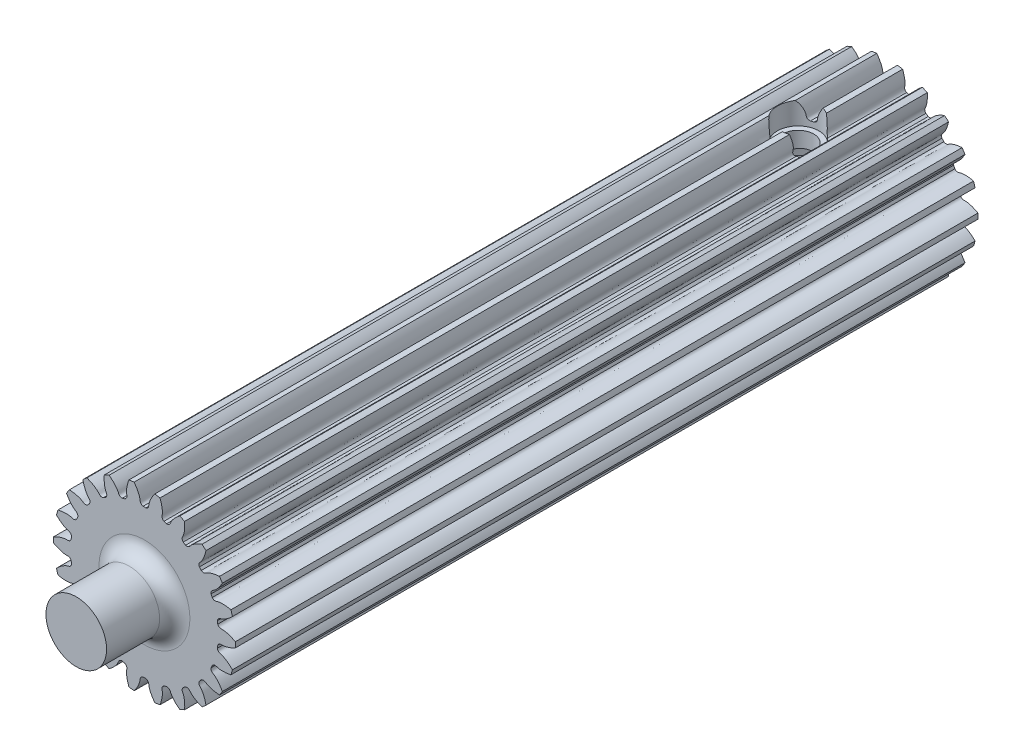
SolidWorks part; units mm, degrees
ref_plane "前视基准面" through (0, 0, 0) normal (0, 0, 1) x (1, 0, 0)
ref_plane "上视基准面" through (0, 0, 0) normal (0, 1, 0) x (1, 0, 0)
ref_plane "右视基准面" through (0, 0, 0) normal (1, 0, 0) x (0, 0, -1)
sketch "草图1" plane through (0, 0, 0) normal (0, 0, 1) x (1, 0, 0)
  circle A0 centre (0, 0) radius 12
extrude "凸台-拉伸1" add sketch "草图1" along normal blind 30
ref_axis "基准轴1" through (0, 0, -1.5) along (0, 0, 1)
sketch "草图2" plane through (0, 0, 0) normal (0, 0, 1) x (1, 0, 0)
  line L0 (0, 0) -> (0, 12) construction
  circle A0 centre (0, 0) radius 12 construction
  arc A1 (0.1857, 9.7482) -> (-0.1857, 9.7482) centre (0, 0) ccw
  arc A2 (3.0856, 13.5599) -> (-3.0856, 13.5599) centre (0, 0) ccw
  spline S0 degree 3 poles (0.1857, 9.7482) (0.5882, 9.8762) (0.5483, 10.1518) (0.5996, 10.4216) (0.606, 10.4519) (0.6139, 10.4862) (0.6235, 10.5243) (0.6349, 10.5661) (0.6484, 10.6117) (0.664, 10.661) (0.6819, 10.7139) (0.7023, 10.7703) (0.7253, 10.8301) (0.7511, 10.8933) (0.7797, 10.9597) (0.8114, 11.0293) (0.8462, 11.1021) (0.8843, 11.1778) (0.9259, 11.2563) (0.9711, 11.3377) (1.0199, 11.4217) (1.0726, 11.5082) (1.1292, 11.5972) (1.1899, 11.6884) (1.2547, 11.7818) (1.3238, 11.8773) (1.3973, 11.9746) (1.4753, 12.0737) (1.5579, 12.1744) (1.6452, 12.2766) (1.7372, 12.3802) (1.8341, 12.4849) (1.9359, 12.5906) (2.0428, 12.6972) (2.1547, 12.8044) (2.2718, 12.9123) (2.3942, 13.0205) (2.5218, 13.1289) (2.6548, 13.2373) (2.8415, 13.3834) (2.9864, 13.49) (3.0856, 13.5599) knots 0 0 0 0 0.157021 0.162531 0.168888 0.176093 0.184146 0.193046 0.202794 0.213389 0.224833 0.237123 0.250262 0.264248 0.279082 0.294763 0.311292 0.328669 0.346893 0.365965 0.385884 0.406652 0.428266 0.450729 0.474039 0.498197 0.523202 0.549055 0.575756 0.603304 0.6317 0.660944 0.691035 0.721974 0.75376 0.786395 0.819876 0.854206 0.889383 0.925408 1 1 1 1
  spline S1 degree 3 poles (-0.1857, 9.7482) (-0.5882, 9.8762) (-0.5483, 10.1518) (-0.5996, 10.4216) (-0.606, 10.4519) (-0.6139, 10.4862) (-0.6235, 10.5243) (-0.6349, 10.5661) (-0.6484, 10.6117) (-0.664, 10.661) (-0.6819, 10.7139) (-0.7023, 10.7703) (-0.7253, 10.8301) (-0.7511, 10.8933) (-0.7797, 10.9597) (-0.8114, 11.0293) (-0.8462, 11.1021) (-0.8843, 11.1778) (-0.9259, 11.2563) (-0.9711, 11.3377) (-1.0199, 11.4217) (-1.0726, 11.5082) (-1.1292, 11.5972) (-1.1899, 11.6884) (-1.2547, 11.7818) (-1.3238, 11.8773) (-1.3973, 11.9746) (-1.4753, 12.0737) (-1.5579, 12.1744) (-1.6452, 12.2766) (-1.7372, 12.3802) (-1.8341, 12.4849) (-1.9359, 12.5906) (-2.0428, 12.6972) (-2.1547, 12.8044) (-2.2718, 12.9123) (-2.3942, 13.0205) (-2.5218, 13.1289) (-2.6548, 13.2373) (-2.8415, 13.3834) (-2.9864, 13.49) (-3.0856, 13.5599) knots 0 0 0 0 0.157021 0.162531 0.168888 0.176093 0.184146 0.193046 0.202794 0.213389 0.224833 0.237123 0.250262 0.264248 0.279082 0.294763 0.311292 0.328669 0.346893 0.365965 0.385884 0.406652 0.428266 0.450729 0.474039 0.498197 0.523202 0.549055 0.575756 0.603304 0.6317 0.660944 0.691035 0.721974 0.75376 0.786395 0.819876 0.854206 0.889383 0.925408 1 1 1 1
extrude "切除-拉伸1" cut sketch "草图2" along normal through all
pattern_circular "阵列(圆周)1" count 22 every 16.364 about axis through (0, 0, -1.5) along (0, 0, 1) of "切除-拉伸1"
sketch "草图3" plane through (0, 0, 0) normal (0, 0, 1) x (1, 0, 0)
  circle A0 centre (0, 0) radius 11 construction
  dimension "Dn" = 22
sketch "草图4" plane through (0, 0, 0) normal (0, 0, -1) x (-1, 0, 0)
  arc A45 (2.9245, 9.3011) -> (2.5682, 9.4057) centre (0, 0) ccw
  arc A46 (2.0557, 11.8226) -> (1.3584, 11.9229) centre (0, 0) ccw
  arc A47 (0.1857, 9.7482) -> (-0.1857, 9.7482) centre (0, 0) ccw
  arc A48 (-1.3584, 11.9229) -> (-2.0557, 11.8226) centre (0, 0) ccw
  arc A49 (-2.5682, 9.4057) -> (-2.9245, 9.3011) centre (0, 0) ccw
  arc A50 (-4.6624, 11.0572) -> (-5.3032, 10.7646) centre (0, 0) ccw
  arc A51 (-5.1141, 8.3011) -> (-5.4265, 8.1004) centre (0, 0) ccw
  arc A52 (-7.5887, 9.2958) -> (-8.1211, 8.8344) centre (0, 0) ccw
  arc A53 (-7.2456, 6.5241) -> (-7.4888, 6.2434) centre (0, 0) ccw
  arc A54 (-9.9003, 6.7812) -> (-10.2811, 6.1886) centre (0, 0) ccw
  arc A55 (-8.7902, 4.2184) -> (-8.9444, 3.8807) centre (0, 0) ccw
  arc A56 (-11.4097, 3.7173) -> (-11.6082, 3.0414) centre (0, 0) ccw
  arc A57 (-9.6226, 1.5711) -> (-9.6754, 1.2035) centre (0, 0) ccw
  arc A58 (-11.9948, 0.3522) -> (-11.9948, -0.3522) centre (0, 0) ccw
  arc A59 (-9.6754, -1.2035) -> (-9.6226, -1.5711) centre (0, 0) ccw
  arc A60 (-11.6082, -3.0414) -> (-11.4097, -3.7173) centre (0, 0) ccw
  arc A61 (-8.9444, -3.8807) -> (-8.7902, -4.2184) centre (0, 0) ccw
  arc A62 (-10.2811, -6.1886) -> (-9.9003, -6.7812) centre (0, 0) ccw
  arc A63 (-7.4888, -6.2434) -> (-7.2456, -6.5241) centre (0, 0) ccw
  arc A64 (-8.1211, -8.8344) -> (-7.5887, -9.2958) centre (0, 0) ccw
  arc A65 (-5.4265, -8.1004) -> (-5.1141, -8.3011) centre (0, 0) ccw
  arc A66 (-5.3032, -10.7646) -> (-4.6624, -11.0572) centre (0, 0) ccw
  arc A67 (-2.9245, -9.3011) -> (-2.5682, -9.4057) centre (0, 0) ccw
  arc A68 (-2.0557, -11.8226) -> (-1.3584, -11.9229) centre (0, 0) ccw
  arc A69 (-0.1857, -9.7482) -> (0.1857, -9.7482) centre (0, 0) ccw
  arc A70 (1.3584, -11.9229) -> (2.0557, -11.8226) centre (0, 0) ccw
  arc A71 (2.5682, -9.4057) -> (2.9245, -9.3011) centre (0, 0) ccw
  arc A72 (4.6624, -11.0572) -> (5.3032, -10.7646) centre (0, 0) ccw
  arc A73 (5.1141, -8.3011) -> (5.4265, -8.1004) centre (0, 0) ccw
  arc A74 (7.5887, -9.2958) -> (8.1211, -8.8344) centre (0, 0) ccw
  arc A75 (7.2456, -6.5241) -> (7.4888, -6.2434) centre (0, 0) ccw
  arc A76 (9.9003, -6.7812) -> (10.2811, -6.1886) centre (0, 0) ccw
  arc A77 (8.7902, -4.2184) -> (8.9444, -3.8807) centre (0, 0) ccw
  arc A78 (11.4097, -3.7173) -> (11.6082, -3.0414) centre (0, 0) ccw
  arc A79 (9.6226, -1.5711) -> (9.6754, -1.2035) centre (0, 0) ccw
  arc A80 (11.9948, -0.3522) -> (11.9948, 0.3522) centre (0, 0) ccw
  arc A81 (9.6754, 1.2035) -> (9.6226, 1.5711) centre (0, 0) ccw
  arc A82 (11.6082, 3.0414) -> (11.4097, 3.7173) centre (0, 0) ccw
  arc A83 (8.9444, 3.8807) -> (8.7902, 4.2184) centre (0, 0) ccw
  arc A84 (10.2811, 6.1886) -> (9.9003, 6.7812) centre (0, 0) ccw
  arc A85 (7.4888, 6.2434) -> (7.2456, 6.5241) centre (0, 0) ccw
  arc A86 (8.1211, 8.8344) -> (7.5887, 9.2958) centre (0, 0) ccw
  arc A87 (5.4265, 8.1004) -> (5.1141, 8.3011) centre (0, 0) ccw
  arc A88 (5.3032, 10.7646) -> (4.6624, 11.0572) centre (0, 0) ccw
  arc A89 (2.9245, 9.3011) -> (2.5682, 9.4057) centre (0, 0) ccw
  arc A90 (2.0557, 11.8226) -> (1.3584, 11.9229) centre (0, 0) ccw
  arc A91 (0.1857, 9.7482) -> (-0.1857, 9.7482) centre (0, 0) ccw
  arc A92 (-1.3584, 11.9229) -> (-2.0557, 11.8226) centre (0, 0) ccw
  arc A93 (-2.5682, 9.4057) -> (-2.9245, 9.3011) centre (0, 0) ccw
  arc A94 (-4.6624, 11.0572) -> (-5.3032, 10.7646) centre (0, 0) ccw
  arc A95 (-5.1141, 8.3011) -> (-5.4265, 8.1004) centre (0, 0) ccw
  arc A96 (-7.5887, 9.2958) -> (-8.1211, 8.8344) centre (0, 0) ccw
  arc A97 (-7.2456, 6.5241) -> (-7.4888, 6.2434) centre (0, 0) ccw
  arc A98 (-9.9003, 6.7812) -> (-10.2811, 6.1886) centre (0, 0) ccw
  arc A99 (-8.7902, 4.2184) -> (-8.9444, 3.8807) centre (0, 0) ccw
  arc A100 (-11.4097, 3.7173) -> (-11.6082, 3.0414) centre (0, 0) ccw
  arc A101 (-9.6226, 1.5711) -> (-9.6754, 1.2035) centre (0, 0) ccw
  arc A102 (-11.9948, 0.3522) -> (-11.9948, -0.3522) centre (0, 0) ccw
  arc A103 (-9.6754, -1.2035) -> (-9.6226, -1.5711) centre (0, 0) ccw
  arc A104 (-11.6082, -3.0414) -> (-11.4097, -3.7173) centre (0, 0) ccw
  arc A105 (-8.9444, -3.8807) -> (-8.7902, -4.2184) centre (0, 0) ccw
  arc A106 (-10.2811, -6.1886) -> (-9.9003, -6.7812) centre (0, 0) ccw
  arc A107 (-7.4888, -6.2434) -> (-7.2456, -6.5241) centre (0, 0) ccw
  arc A108 (-8.1211, -8.8344) -> (-7.5887, -9.2958) centre (0, 0) ccw
  arc A109 (-5.4265, -8.1004) -> (-5.1141, -8.3011) centre (0, 0) ccw
  arc A110 (-5.3032, -10.7646) -> (-4.6624, -11.0572) centre (0, 0) ccw
  arc A111 (-2.9245, -9.3011) -> (-2.5682, -9.4057) centre (0, 0) ccw
  arc A112 (-2.0557, -11.8226) -> (-1.3584, -11.9229) centre (0, 0) ccw
  arc A113 (-0.1857, -9.7482) -> (0.1857, -9.7482) centre (0, 0) ccw
  arc A114 (1.3584, -11.9229) -> (2.0557, -11.8226) centre (0, 0) ccw
  arc A115 (2.5682, -9.4057) -> (2.9245, -9.3011) centre (0, 0) ccw
  arc A116 (4.6624, -11.0572) -> (5.3032, -10.7646) centre (0, 0) ccw
  arc A117 (5.1141, -8.3011) -> (5.4265, -8.1004) centre (0, 0) ccw
  arc A118 (7.5887, -9.2958) -> (8.1211, -8.8344) centre (0, 0) ccw
  arc A119 (7.2456, -6.5241) -> (7.4888, -6.2434) centre (0, 0) ccw
  arc A120 (9.9003, -6.7812) -> (10.2811, -6.1886) centre (0, 0) ccw
  arc A121 (8.7902, -4.2184) -> (8.9444, -3.8807) centre (0, 0) ccw
  arc A122 (11.4097, -3.7173) -> (11.6082, -3.0414) centre (0, 0) ccw
  arc A123 (9.6226, -1.5711) -> (9.6754, -1.2035) centre (0, 0) ccw
  arc A124 (11.9948, -0.3522) -> (11.9948, 0.3522) centre (0, 0) ccw
  arc A125 (9.6754, 1.2035) -> (9.6226, 1.5711) centre (0, 0) ccw
  arc A126 (11.6082, 3.0414) -> (11.4097, 3.7173) centre (0, 0) ccw
  arc A127 (8.9444, 3.8807) -> (8.7902, 4.2184) centre (0, 0) ccw
  arc A128 (10.2811, 6.1886) -> (9.9003, 6.7812) centre (0, 0) ccw
  arc A129 (7.4888, 6.2434) -> (7.2456, 6.5241) centre (0, 0) ccw
  arc A130 (8.1211, 8.8344) -> (7.5887, 9.2958) centre (0, 0) ccw
  arc A131 (5.4265, 8.1004) -> (5.1141, 8.3011) centre (0, 0) ccw
  arc A132 (5.3032, 10.7646) -> (4.6624, 11.0572) centre (0, 0) ccw
  spline S44 degree 3 poles (-9364.1406, 3504.5844) (256.9535, -188.5881) (30.391, 33.0955) (4.2738, 10.7434) (4.1283, 10.6084) (3.9999, 10.4794) (3.888, 10.3576) (3.7917, 10.2441) (3.7102, 10.1398) (3.6518, 10.0587) (3.6037, 9.9872) (3.5713, 9.9359) (3.5381, 9.8795) (3.5167, 9.8409) (0.4171, 3.7881) (50.6224, -28.8281) (-8414.4505, 5403.2739) knots -20.504077 -20.504077 -20.504077 -20.504077 0.549271 0.593348 0.634035 0.671331 0.705237 0.735752 0.762877 0.786611 0.797206 0.815854 0.823907 0.837469 0.842979 5.006087 5.006087 5.006087 5.006087 only from (4.6624, 11.0572) to (2.9245, 9.3011)
  spline S45 degree 3 poles (9998.4358, -3.6711) (-58.166, 3.1168) (1.6971, 3.4126) (2.3619, 10.18) (2.3658, 10.2385) (2.3681, 10.3211) (2.3668, 10.4204) (2.3608, 10.536) (2.3486, 10.6678) (2.329, 10.8154) (2.3007, 10.9784) (2.2624, 11.1562) (2.213, 11.3485) (2.1511, 11.5544) (-9.7414, 46.086) (-333.2574, -33.7791) (9782.7718, -2064.5446) knots -4.005883 -4.005883 -4.005883 -4.005883 0.157021 0.162531 0.176093 0.193046 0.213389 0.237123 0.264248 0.294763 0.328669 0.365965 0.406652 0.450729 0.498197 22.864222 22.864222 22.864222 22.864222 only from (2.5682, 9.4057) to (2.0557, 11.8226)
  spline S46 degree 3 poles (-9972.1826, 724.4408) (299.6765, -108.5568) (19.8359, 40.317) (1.0739, 11.5123) (0.9723, 11.3417) (0.8855, 11.1818) (0.8124, 11.0334) (0.752, 10.8973) (0.7032, 10.7743) (0.6701, 10.6801) (0.644, 10.5979) (0.6274, 10.5396) (0.6113, 10.4761) (0.6018, 10.4331) (-0.667, 3.7521) (56.6936, -13.3983) (-9595.8843, 2813.7787) knots -20.504077 -20.504077 -20.504077 -20.504077 0.549271 0.593348 0.634035 0.671331 0.705237 0.735752 0.762877 0.786611 0.797206 0.815854 0.823907 0.837469 0.842979 5.006087 5.006087 5.006087 5.006087 only from (1.3584, 11.9229) to (0.1857, 9.7482)
  spline S47 degree 3 poles (9594.4631, 2813.3625) (-56.688, -13.3967) (0.6669, 3.7525) (-0.6018, 10.4331) (-0.6145, 10.4903) (-0.6356, 10.5702) (-0.6648, 10.6651) (-0.7032, 10.7743) (-0.752, 10.8973) (-0.8124, 11.0334) (-0.8855, 11.1818) (-0.9723, 11.3417) (-1.0739, 11.5123) (-1.1913, 11.6924) (-22.3307, 41.4748) (-310.2415, -126.3003) (9968.1502, 775.2093) knots -4.005883 -4.005883 -4.005883 -4.005883 0.157021 0.162531 0.176093 0.193046 0.213389 0.237123 0.264248 0.294763 0.328669 0.365965 0.406652 0.450729 0.498197 22.864222 22.864222 22.864222 22.864222 only from (-0.1857, 9.7482) to (-1.3584, 11.9229)
  spline S48 degree 3 poles (-9772.3377, -2114.3927) (318.1215, -19.7309) (7.6738, 44.2723) (-2.213, 11.3485) (-2.2624, 11.1562) (-2.3007, 10.9784) (-2.329, 10.8154) (-2.3486, 10.6678) (-2.3608, 10.536) (-2.366, 10.4362) (-2.3678, 10.3501) (-2.3674, 10.2894) (-2.3649, 10.224) (-2.3619, 10.18) (-1.6971, 3.4122) (58.1719, 3.1168) (-9999.9166, -3.6721) knots -20.504077 -20.504077 -20.504077 -20.504077 0.549271 0.593348 0.634035 0.671331 0.705237 0.735752 0.762877 0.786611 0.797206 0.815854 0.823907 0.837469 0.842979 5.006087 5.006087 5.006087 5.006087 only from (-2.0557, 11.8226) to (-2.5682, 9.4057)
  spline S49 degree 3 poles (8413.2042, 5402.4742) (-50.6175, -28.8249) (-0.4173, 3.7884) (-3.5167, 9.8409) (-3.5451, 9.8922) (-3.5879, 9.963) (-3.6426, 10.0458) (-3.7102, 10.1398) (-3.7917, 10.2441) (-3.888, 10.3576) (-3.9999, 10.4794) (-4.1283, 10.6084) (-4.2738, 10.7434) (-4.4372, 10.8832) (-33.111, 33.5035) (-262.0916, -208.5894) (9345.9684, 3552.1603) knots -4.005883 -4.005883 -4.005883 -4.005883 0.157021 0.162531 0.176093 0.193046 0.213389 0.237123 0.264248 0.294763 0.328669 0.365965 0.406652 0.450729 0.498197 22.864222 22.864222 22.864222 22.864222 only from (-2.9245, 9.3011) to (-4.6624, 11.0572)
  spline S50 degree 3 poles (-8780.7961, -4781.9306) (310.7942, 70.6936) (-5.11, 44.6409) (-5.3206, 10.2653) (-5.3138, 10.0669) (-5.3004, 9.8855) (-5.2817, 9.7211) (-5.2589, 9.574) (-5.2335, 9.4441) (-5.2104, 9.3469) (-5.1879, 9.2637) (-5.1704, 9.2057) (-5.1495, 9.1436) (-5.1343, 9.1022) (-2.5897, 2.7959) (54.9374, 19.3795) (-9593.8152, -2820.8254) knots -20.504077 -20.504077 -20.504077 -20.504077 0.549271 0.593348 0.634035 0.671331 0.705237 0.735752 0.762877 0.786611 0.797206 0.815854 0.823907 0.837469 0.842979 5.006087 5.006087 5.006087 5.006087 only from (-5.3032, 10.7646) to (-5.1141, 8.3011)
  spline S51 degree 3 poles (6550.3574, 7553.9095) (-40.4462, -41.9178) (-1.4677, 3.5173) (-6.1468, 8.4515) (-6.1884, 8.4928) (-6.2494, 8.5486) (-6.3253, 8.6126) (-6.4166, 8.6838) (-6.5242, 8.7609) (-6.6486, 8.8427) (-6.7903, 8.928) (-6.9498, 9.0156) (-7.1274, 9.1041) (-7.3236, 9.1923) (-41.2087, 22.8179) (-192.7087, -273.9798) (7966.6318, 6041.3364) knots -4.005883 -4.005883 -4.005883 -4.005883 0.157021 0.162531 0.176093 0.193046 0.213389 0.237123 0.264248 0.294763 0.328669 0.365965 0.406652 0.450729 0.498197 22.864222 22.864222 22.864222 22.864222 only from (-5.4265, 8.1004) to (-7.5887, 9.2958)
  spline S52 degree 3 poles (-7077.8866, -7062.0649) (278.2882, 155.3908) (-17.4798, 41.393) (-7.9971, 8.3505) (-7.9348, 8.1621) (-7.8708, 7.9917) (-7.8065, 7.8393) (-7.7432, 7.7046) (-7.6822, 7.5871) (-7.6327, 7.5003) (-7.5876, 7.4269) (-7.5545, 7.3761) (-7.517, 7.3224) (-7.4907, 7.287) (-3.2725, 1.953) (47.2522, 34.0721) (-8410.4799, -5409.4523) knots -20.504077 -20.504077 -20.504077 -20.504077 0.549271 0.593348 0.634035 0.671331 0.705237 0.735752 0.762877 0.786611 0.797206 0.815854 0.823907 0.837469 0.842979 5.006087 5.006087 5.006087 5.006087 only from (-8.1211, 8.8344) to (-7.2456, 6.5241)
  spline S53 degree 3 poles (4156.8397, 9093.3721) (-26.9982, -51.6149) (-2.3992, 2.9614) (-8.2789, 6.3774) (-8.3304, 6.4053) (-8.4047, 6.4416) (-8.4955, 6.4817) (-8.6032, 6.5243) (-8.7281, 6.5679) (-8.8705, 6.6114) (-9.0305, 6.6533) (-9.2082, 6.6924) (-9.4036, 6.7273) (-9.6167, 6.7566) (-45.968, 10.2838) (-107.7136, -317.174) (5941.8861, 8041.0794) knots -4.005883 -4.005883 -4.005883 -4.005883 0.157021 0.162531 0.176093 0.193046 0.213389 0.237123 0.264248 0.294763 0.328669 0.365965 0.406652 0.450729 0.498197 22.864222 22.864222 22.864222 22.864222 only from (-7.4888, 6.2434) to (-9.9003, 6.7812)
  spline S54 degree 3 poles (-4801.5689, -8770.0728) (223.2369, 227.4992) (-28.4335, 34.7917) (-10.0258, 5.7592) (-9.9129, 5.596) (-9.8035, 5.4506) (-9.6989, 5.3224) (-9.6002, 5.211) (-9.5086, 5.1155) (-9.4366, 5.0462) (-9.3727, 4.9884) (-9.3266, 4.949) (-9.2755, 4.908) (-9.2403, 4.8814) (-3.6901, 0.952) (35.7389, 46.0045) (-6545.7775, -7559.8374) knots -20.504077 -20.504077 -20.504077 -20.504077 0.549271 0.593348 0.634035 0.671331 0.705237 0.735752 0.762877 0.786611 0.797206 0.815854 0.823907 0.837469 0.842979 5.006087 5.006087 5.006087 5.006087 only from (-10.2811, 6.1886) to (-8.7902, 4.2184)
  spline S55 degree 3 poles (1426.5595, 9896.1437) (-11.363, -57.1304) (-3.1363, 2.1655) (-9.7402, 3.7867) (-9.7976, 3.7989) (-9.8791, 3.8128) (-9.9775, 3.8257) (-10.0928, 3.8362) (-10.225, 3.8429) (-10.3738, 3.8445) (-10.5392, 3.8396) (-10.7207, 3.8271) (-10.918, 3.8055) (-11.1307, 3.7736) (-47.0033, -3.0835) (-13.9922, -334.6726) (3435.7641, 9389.3819) knots -4.005883 -4.005883 -4.005883 -4.005883 0.157021 0.162531 0.176093 0.193046 0.213389 0.237123 0.264248 0.294763 0.328669 0.365965 0.406652 0.450729 0.498197 22.864222 22.864222 22.864222 22.864222 only from (-8.9444, 3.8807) to (-11.4097, 3.7173)
  spline S56 degree 3 poles (-2136.2566, -9767.5815) (150.1003, 281.177) (-37.0837, 25.3717) (-11.2422, 2.7013) (-11.0879, 2.5765) (-10.942, 2.4678) (-10.8055, 2.3743) (-10.6794, 2.2952) (-10.5646, 2.2294) (-10.476, 2.1832) (-10.3984, 2.1457) (-10.3431, 2.1209) (-10.2825, 2.096) (-10.2412, 2.0804) (-3.8089, -0.1262) (21.3303, 54.2098) (-4150.7752, -9097.7696) knots -20.504077 -20.504077 -20.504077 -20.504077 0.549271 0.593348 0.634035 0.671331 0.705237 0.735752 0.762877 0.786611 0.797206 0.815854 0.823907 0.837469 0.842979 5.006087 5.006087 5.006087 5.006087 only from (-11.6082, 3.0414) to (-9.6226, 1.5711)
  spline S57 degree 3 poles (-1419.292, 9897.1886) (5.1928, -58.0175) (-3.6193, 1.1942) (-10.4125, 0.8891) (-10.4709, 0.8847) (-10.5531, 0.8751) (-10.6512, 0.8598) (-10.7647, 0.8373) (-10.8934, 0.8065) (-11.0367, 0.7661) (-11.194, 0.7149) (-11.3647, 0.6517) (-11.5479, 0.5754) (-11.743, 0.4849) (-44.2306, -16.2009) (80.8628, -325.0581) (651.2969, 9977.0126) knots -4.005883 -4.005883 -4.005883 -4.005883 0.157021 0.162531 0.176093 0.193046 0.213389 0.237123 0.264248 0.294763 0.328669 0.365965 0.406652 0.450729 0.498197 22.864222 22.864222 22.864222 22.864222 only from (-9.6754, 1.2035) to (-11.9948, 0.3522)
  spline S58 degree 3 poles (702.1225, -9973.7788) (64.8035, 312.0755) (-42.7296, 13.8963) (-11.5479, -0.5754) (-11.3647, -0.6517) (-11.194, -0.7149) (-11.0367, -0.7661) (-10.8934, -0.8065) (-10.7647, -0.8373) (-10.6667, -0.8567) (-10.5817, -0.8708) (-10.5216, -0.879) (-10.4565, -0.8858) (-10.4125, -0.8891) (-3.619, -1.1942) (5.1936, 58.0233) (-1419.5018, -9898.6545) knots -20.504077 -20.504077 -20.504077 -20.504077 0.549271 0.593348 0.634035 0.671331 0.705237 0.735752 0.762877 0.786611 0.797206 0.815854 0.823907 0.837469 0.842979 5.006087 5.006087 5.006087 5.006087 only from (-11.9948, -0.3522) to (-9.6754, -1.2035)
  spline S59 degree 3 poles (-4150.161, 9096.4221) (21.3278, -54.2044) (-3.8092, 0.1261) (-10.2412, -2.0804) (-10.296, -2.1012) (-10.3722, -2.1335) (-10.4619, -2.1758) (-10.5646, -2.2294) (-10.6794, -2.2952) (-10.8055, -2.3743) (-10.942, -2.4678) (-11.0879, -2.5765) (-11.2422, -2.7014) (-11.4039, -2.8432) (-37.8746, -28.0059) (169.1667, -289.1093) (-2185.9344, 9756.365) knots -4.005883 -4.005883 -4.005883 -4.005883 0.157021 0.162531 0.176093 0.193046 0.213389 0.237123 0.264248 0.294763 0.328669 0.365965 0.406652 0.450729 0.498197 22.864222 22.864222 22.864222 22.864222 only from (-9.6226, -1.5711) to (-11.6082, -3.0414)
  spline S60 degree 3 poles (3483.6198, -9371.9599) (-25.7434, 317.6915) (-44.9138, 1.2951) (-10.918, -3.8055) (-10.7207, -3.8271) (-10.5392, -3.8396) (-10.3738, -3.8445) (-10.225, -3.8429) (-10.0928, -3.8362) (-9.9933, -3.8272) (-9.9078, -3.8167) (-9.8478, -3.8076) (-9.7834, -3.7958) (-9.7402, -3.7867) (-3.136, -2.1654) (-11.3638, 57.1362) (1426.7712, -9897.6093) knots -20.504077 -20.504077 -20.504077 -20.504077 0.549271 0.593348 0.634035 0.671331 0.705237 0.735752 0.762877 0.786611 0.797206 0.815854 0.823907 0.837469 0.842979 5.006087 5.006087 5.006087 5.006087 only from (-11.4097, -3.7173) to (-8.9444, -3.8807)
  spline S61 degree 3 poles (-6544.8086, 7558.7176) (35.7351, -46) (-3.6904, -0.9522) (-9.2403, -4.8814) (-9.287, -4.9168) (-9.351, -4.9692) (-9.4251, -5.0352) (-9.5086, -5.1155) (-9.6002, -5.211) (-9.6989, -5.3224) (-9.8035, -5.4506) (-9.9129, -5.596) (-10.0258, -5.7592) (-10.1409, -5.9408) (-28.4503, -37.542) (243.7658, -229.7385) (-4846.0744, 8745.3148) knots -4.005883 -4.005883 -4.005883 -4.005883 0.157021 0.162531 0.176093 0.193046 0.213389 0.237123 0.264248 0.294763 0.328669 0.365965 0.406652 0.450729 0.498197 22.864222 22.864222 22.864222 22.864222 only from (-8.7902, -4.2184) to (-10.2811, -6.1886)
  spline S62 degree 3 poles (5982.895, -8010.8806) (-114.2046, 297.57) (-43.4593, -11.4111) (-9.4036, -6.7273) (-9.2082, -6.6924) (-9.0305, -6.6533) (-8.8705, -6.6114) (-8.7281, -6.5679) (-8.6032, -6.5243) (-8.5102, -6.4876) (-8.4311, -6.4535) (-8.3761, -6.4279) (-8.3177, -6.3984) (-8.2789, -6.3774) (-2.3989, -2.9612) (-27.0006, 51.6202) (4157.4558, -9094.7187) knots -20.504077 -20.504077 -20.504077 -20.504077 0.549271 0.593348 0.634035 0.671331 0.705237 0.735752 0.762877 0.786611 0.797206 0.815854 0.823907 0.837469 0.842979 5.006087 5.006087 5.006087 5.006087 only from (-9.9003, -6.7812) to (-7.4888, -6.2434)
  spline S63 degree 3 poles (-8409.2347, 5408.6508) (47.2473, -34.069) (-3.2727, -1.9533) (-7.4907, -7.287) (-7.5256, -7.3341) (-7.5722, -7.4024) (-7.6248, -7.4866) (-7.6822, -7.5871) (-7.7432, -7.7046) (-7.8065, -7.8393) (-7.8708, -7.9917) (-7.9348, -8.1621) (-7.9971, -8.3505) (-8.0564, -8.5572) (-16.721, -44.0366) (298.6164, -151.7558) (-7113.6142, 7025.7712) knots -4.005883 -4.005883 -4.005883 -4.005883 0.157021 0.162531 0.176093 0.193046 0.213389 0.237123 0.264248 0.294763 0.328669 0.365965 0.406652 0.450729 0.498197 22.864222 22.864222 22.864222 22.864222 only from (-7.2456, -6.5241) to (-8.1211, -8.8344)
  spline S64 degree 3 poles (7997.4716, -6000.8073) (-193.4137, 253.3412) (-38.484, -23.1927) (-7.1274, -9.1041) (-6.9498, -9.0156) (-6.7903, -8.928) (-6.6486, -8.8427) (-6.5242, -8.7609) (-6.4166, -8.6838) (-6.3378, -8.6224) (-6.2715, -8.5674) (-6.2259, -8.5273) (-6.1781, -8.4826) (-6.1468, -8.4515) (-1.4674, -3.5171) (-40.45, 41.9223) (6551.3279, -7555.028) knots -20.504077 -20.504077 -20.504077 -20.504077 0.549271 0.593348 0.634035 0.671331 0.705237 0.735752 0.762877 0.786611 0.797206 0.815854 0.823907 0.837469 0.842979 5.006087 5.006087 5.006087 5.006087 only from (-7.5887, -9.2958) to (-5.4265, -8.1004)
  spline S65 degree 3 poles (-9592.3946, 2820.4073) (54.9318, -19.3779) (-2.5898, -2.7962) (-5.1343, -9.1022) (-5.1545, -9.1572) (-5.18, -9.2359) (-5.2067, -9.3315) (-5.2335, -9.4441) (-5.2589, -9.574) (-5.2817, -9.7211) (-5.3004, -9.8855) (-5.3138, -10.0669) (-5.3206, -10.2653) (-5.3192, -10.4804) (-3.6372, -46.9637) (329.2748, -61.4786) (-8804.8513, 4737.0413) knots -4.005883 -4.005883 -4.005883 -4.005883 0.157021 0.162531 0.176093 0.193046 0.213389 0.237123 0.264248 0.294763 0.328669 0.365965 0.406652 0.450729 0.498197 22.864222 22.864222 22.864222 22.864222 only from (-5.1141, -8.3011) to (-5.3032, -10.7646)
  spline S66 degree 3 poles (9364.1406, -3504.5844) (-256.9535, 188.5881) (-30.391, -33.0955) (-4.2738, -10.7434) (-4.1283, -10.6084) (-3.9999, -10.4794) (-3.888, -10.3576) (-3.7917, -10.2441) (-3.7102, -10.1398) (-3.6518, -10.0587) (-3.6037, -9.9872) (-3.5713, -9.9359) (-3.5381, -9.8795) (-3.5167, -9.8409) (-0.4171, -3.7881) (-50.6224, 28.8281) (8414.4505, -5403.2739) knots -20.504077 -20.504077 -20.504077 -20.504077 0.549271 0.593348 0.634035 0.671331 0.705237 0.735752 0.762877 0.786611 0.797206 0.815854 0.823907 0.837469 0.842979 5.006087 5.006087 5.006087 5.006087 only from (-4.6624, -11.0572) to (-2.9245, -9.3011)
  spline S67 degree 3 poles (-9998.4358, 3.6711) (58.166, -3.1168) (-1.6971, -3.4126) (-2.3619, -10.18) (-2.3658, -10.2385) (-2.3681, -10.3211) (-2.3668, -10.4204) (-2.3608, -10.536) (-2.3486, -10.6678) (-2.329, -10.8154) (-2.3007, -10.9784) (-2.2624, -11.1562) (-2.213, -11.3485) (-2.1511, -11.5544) (9.7414, -46.086) (333.2574, 33.7791) (-9782.7718, 2064.5446) knots -4.005883 -4.005883 -4.005883 -4.005883 0.157021 0.162531 0.176093 0.193046 0.213389 0.237123 0.264248 0.294763 0.328669 0.365965 0.406652 0.450729 0.498197 22.864222 22.864222 22.864222 22.864222 only from (-2.5682, -9.4057) to (-2.0557, -11.8226)
  spline S68 degree 3 poles (9972.1826, -724.4408) (-299.6765, 108.5568) (-19.8359, -40.317) (-1.0739, -11.5123) (-0.9723, -11.3417) (-0.8855, -11.1818) (-0.8124, -11.0334) (-0.752, -10.8973) (-0.7032, -10.7743) (-0.6701, -10.6801) (-0.644, -10.5979) (-0.6274, -10.5396) (-0.6113, -10.4761) (-0.6018, -10.4331) (0.667, -3.7521) (-56.6936, 13.3983) (9595.8843, -2813.7787) knots -20.504077 -20.504077 -20.504077 -20.504077 0.549271 0.593348 0.634035 0.671331 0.705237 0.735752 0.762877 0.786611 0.797206 0.815854 0.823907 0.837469 0.842979 5.006087 5.006087 5.006087 5.006087 only from (-1.3584, -11.9229) to (-0.1857, -9.7482)
  spline S69 degree 3 poles (-9594.4631, -2813.3625) (56.688, 13.3967) (-0.6669, -3.7525) (0.6018, -10.4331) (0.6145, -10.4903) (0.6356, -10.5702) (0.6648, -10.6651) (0.7032, -10.7743) (0.752, -10.8973) (0.8124, -11.0334) (0.8855, -11.1818) (0.9723, -11.3417) (1.0739, -11.5123) (1.1913, -11.6924) (22.3307, -41.4748) (310.2415, 126.3003) (-9968.1502, -775.2093) knots -4.005883 -4.005883 -4.005883 -4.005883 0.157021 0.162531 0.176093 0.193046 0.213389 0.237123 0.264248 0.294763 0.328669 0.365965 0.406652 0.450729 0.498197 22.864222 22.864222 22.864222 22.864222 only from (0.1857, -9.7482) to (1.3584, -11.9229)
  spline S70 degree 3 poles (9772.3377, 2114.3927) (-318.1215, 19.7309) (-7.6738, -44.2723) (2.213, -11.3485) (2.2624, -11.1562) (2.3007, -10.9784) (2.329, -10.8154) (2.3486, -10.6678) (2.3608, -10.536) (2.366, -10.4362) (2.3678, -10.3501) (2.3674, -10.2894) (2.3649, -10.224) (2.3619, -10.18) (1.6971, -3.4122) (-58.1719, -3.1168) (9999.9166, 3.6721) knots -20.504077 -20.504077 -20.504077 -20.504077 0.549271 0.593348 0.634035 0.671331 0.705237 0.735752 0.762877 0.786611 0.797206 0.815854 0.823907 0.837469 0.842979 5.006087 5.006087 5.006087 5.006087 only from (2.0557, -11.8226) to (2.5682, -9.4057)
  spline S71 degree 3 poles (-8413.2042, -5402.4742) (50.6175, 28.8249) (0.4173, -3.7884) (3.5167, -9.8409) (3.5451, -9.8922) (3.5879, -9.963) (3.6426, -10.0458) (3.7102, -10.1398) (3.7917, -10.2441) (3.888, -10.3576) (3.9999, -10.4794) (4.1283, -10.6084) (4.2738, -10.7434) (4.4372, -10.8832) (33.111, -33.5035) (262.0916, 208.5894) (-9345.9684, -3552.1603) knots -4.005883 -4.005883 -4.005883 -4.005883 0.157021 0.162531 0.176093 0.193046 0.213389 0.237123 0.264248 0.294763 0.328669 0.365965 0.406652 0.450729 0.498197 22.864222 22.864222 22.864222 22.864222 only from (2.9245, -9.3011) to (4.6624, -11.0572)
  spline S72 degree 3 poles (8780.7961, 4781.9306) (-310.7942, -70.6936) (5.11, -44.6409) (5.3206, -10.2653) (5.3138, -10.0669) (5.3004, -9.8855) (5.2817, -9.7211) (5.2589, -9.574) (5.2335, -9.4441) (5.2104, -9.3469) (5.1879, -9.2637) (5.1704, -9.2057) (5.1495, -9.1436) (5.1343, -9.1022) (2.5897, -2.7959) (-54.9374, -19.3795) (9593.8152, 2820.8254) knots -20.504077 -20.504077 -20.504077 -20.504077 0.549271 0.593348 0.634035 0.671331 0.705237 0.735752 0.762877 0.786611 0.797206 0.815854 0.823907 0.837469 0.842979 5.006087 5.006087 5.006087 5.006087 only from (5.3032, -10.7646) to (5.1141, -8.3011)
  spline S73 degree 3 poles (-6550.3574, -7553.9095) (40.4462, 41.9178) (1.4677, -3.5173) (6.1468, -8.4515) (6.1884, -8.4928) (6.2494, -8.5486) (6.3253, -8.6126) (6.4166, -8.6838) (6.5242, -8.7609) (6.6486, -8.8427) (6.7903, -8.928) (6.9498, -9.0156) (7.1274, -9.1041) (7.3236, -9.1923) (41.2087, -22.8179) (192.7087, 273.9798) (-7966.6318, -6041.3364) knots -4.005883 -4.005883 -4.005883 -4.005883 0.157021 0.162531 0.176093 0.193046 0.213389 0.237123 0.264248 0.294763 0.328669 0.365965 0.406652 0.450729 0.498197 22.864222 22.864222 22.864222 22.864222 only from (5.4265, -8.1004) to (7.5887, -9.2958)
  spline S74 degree 3 poles (7077.8866, 7062.0649) (-278.2882, -155.3908) (17.4798, -41.393) (7.9971, -8.3505) (7.9348, -8.1621) (7.8708, -7.9917) (7.8065, -7.8393) (7.7432, -7.7046) (7.6822, -7.5871) (7.6327, -7.5003) (7.5876, -7.4269) (7.5545, -7.3761) (7.517, -7.3224) (7.4907, -7.287) (3.2725, -1.953) (-47.2522, -34.0721) (8410.4799, 5409.4523) knots -20.504077 -20.504077 -20.504077 -20.504077 0.549271 0.593348 0.634035 0.671331 0.705237 0.735752 0.762877 0.786611 0.797206 0.815854 0.823907 0.837469 0.842979 5.006087 5.006087 5.006087 5.006087 only from (8.1211, -8.8344) to (7.2456, -6.5241)
  spline S75 degree 3 poles (-4156.8397, -9093.3721) (26.9982, 51.6149) (2.3992, -2.9614) (8.2789, -6.3774) (8.3304, -6.4053) (8.4047, -6.4416) (8.4955, -6.4817) (8.6032, -6.5243) (8.7281, -6.5679) (8.8705, -6.6114) (9.0305, -6.6533) (9.2082, -6.6924) (9.4036, -6.7273) (9.6167, -6.7566) (45.968, -10.2838) (107.7136, 317.174) (-5941.8861, -8041.0794) knots -4.005883 -4.005883 -4.005883 -4.005883 0.157021 0.162531 0.176093 0.193046 0.213389 0.237123 0.264248 0.294763 0.328669 0.365965 0.406652 0.450729 0.498197 22.864222 22.864222 22.864222 22.864222 only from (7.4888, -6.2434) to (9.9003, -6.7812)
  spline S76 degree 3 poles (4801.5689, 8770.0728) (-223.2369, -227.4992) (28.4335, -34.7917) (10.0258, -5.7592) (9.9129, -5.596) (9.8035, -5.4506) (9.6989, -5.3224) (9.6002, -5.211) (9.5086, -5.1155) (9.4366, -5.0462) (9.3727, -4.9884) (9.3266, -4.949) (9.2755, -4.908) (9.2403, -4.8814) (3.6901, -0.952) (-35.7389, -46.0045) (6545.7775, 7559.8374) knots -20.504077 -20.504077 -20.504077 -20.504077 0.549271 0.593348 0.634035 0.671331 0.705237 0.735752 0.762877 0.786611 0.797206 0.815854 0.823907 0.837469 0.842979 5.006087 5.006087 5.006087 5.006087 only from (10.2811, -6.1886) to (8.7902, -4.2184)
  spline S77 degree 3 poles (-1426.5595, -9896.1437) (11.363, 57.1304) (3.1363, -2.1655) (9.7402, -3.7867) (9.7976, -3.7989) (9.8791, -3.8128) (9.9775, -3.8257) (10.0928, -3.8362) (10.225, -3.8429) (10.3738, -3.8445) (10.5392, -3.8396) (10.7207, -3.8271) (10.918, -3.8055) (11.1307, -3.7736) (47.0033, 3.0835) (13.9922, 334.6726) (-3435.7641, -9389.3819) knots -4.005883 -4.005883 -4.005883 -4.005883 0.157021 0.162531 0.176093 0.193046 0.213389 0.237123 0.264248 0.294763 0.328669 0.365965 0.406652 0.450729 0.498197 22.864222 22.864222 22.864222 22.864222 only from (8.9444, -3.8807) to (11.4097, -3.7173)
  spline S78 degree 3 poles (2136.2566, 9767.5815) (-150.1003, -281.177) (37.0837, -25.3717) (11.2422, -2.7013) (11.0879, -2.5765) (10.942, -2.4678) (10.8055, -2.3743) (10.6794, -2.2952) (10.5646, -2.2294) (10.476, -2.1832) (10.3984, -2.1457) (10.3431, -2.1209) (10.2825, -2.096) (10.2412, -2.0804) (3.8089, 0.1262) (-21.3303, -54.2098) (4150.7752, 9097.7696) knots -20.504077 -20.504077 -20.504077 -20.504077 0.549271 0.593348 0.634035 0.671331 0.705237 0.735752 0.762877 0.786611 0.797206 0.815854 0.823907 0.837469 0.842979 5.006087 5.006087 5.006087 5.006087 only from (11.6082, -3.0414) to (9.6226, -1.5711)
  spline S79 degree 3 poles (1419.292, -9897.1886) (-5.1928, 58.0175) (3.6193, -1.1942) (10.4125, -0.8891) (10.4709, -0.8847) (10.5531, -0.8751) (10.6512, -0.8598) (10.7647, -0.8373) (10.8934, -0.8065) (11.0367, -0.7661) (11.194, -0.7149) (11.3647, -0.6517) (11.5479, -0.5754) (11.743, -0.4849) (44.2306, 16.2009) (-80.8628, 325.0581) (-651.2969, -9977.0126) knots -4.005883 -4.005883 -4.005883 -4.005883 0.157021 0.162531 0.176093 0.193046 0.213389 0.237123 0.264248 0.294763 0.328669 0.365965 0.406652 0.450729 0.498197 22.864222 22.864222 22.864222 22.864222 only from (9.6754, -1.2035) to (11.9948, -0.3522)
  spline S80 degree 3 poles (-702.1225, 9973.7788) (-64.8035, -312.0755) (42.7296, -13.8963) (11.5479, 0.5754) (11.3647, 0.6517) (11.194, 0.7149) (11.0367, 0.7661) (10.8934, 0.8065) (10.7647, 0.8373) (10.6667, 0.8567) (10.5817, 0.8708) (10.5216, 0.879) (10.4565, 0.8858) (10.4125, 0.8891) (3.619, 1.1942) (-5.1936, -58.0233) (1419.5018, 9898.6545) knots -20.504077 -20.504077 -20.504077 -20.504077 0.549271 0.593348 0.634035 0.671331 0.705237 0.735752 0.762877 0.786611 0.797206 0.815854 0.823907 0.837469 0.842979 5.006087 5.006087 5.006087 5.006087 only from (11.9948, 0.3522) to (9.6754, 1.2035)
  spline S81 degree 3 poles (4150.161, -9096.4221) (-21.3278, 54.2044) (3.8092, -0.1261) (10.2412, 2.0804) (10.296, 2.1012) (10.3722, 2.1335) (10.4619, 2.1758) (10.5646, 2.2294) (10.6794, 2.2952) (10.8055, 2.3743) (10.942, 2.4678) (11.0879, 2.5765) (11.2422, 2.7014) (11.4039, 2.8432) (37.8746, 28.0059) (-169.1667, 289.1093) (2185.9344, -9756.365) knots -4.005883 -4.005883 -4.005883 -4.005883 0.157021 0.162531 0.176093 0.193046 0.213389 0.237123 0.264248 0.294763 0.328669 0.365965 0.406652 0.450729 0.498197 22.864222 22.864222 22.864222 22.864222 only from (9.6226, 1.5711) to (11.6082, 3.0414)
  spline S82 degree 3 poles (-3483.6198, 9371.9599) (25.7434, -317.6915) (44.9138, -1.2951) (10.918, 3.8055) (10.7207, 3.8271) (10.5392, 3.8396) (10.3738, 3.8445) (10.225, 3.8429) (10.0928, 3.8362) (9.9933, 3.8272) (9.9078, 3.8167) (9.8478, 3.8076) (9.7834, 3.7958) (9.7402, 3.7867) (3.136, 2.1654) (11.3638, -57.1362) (-1426.7712, 9897.6093) knots -20.504077 -20.504077 -20.504077 -20.504077 0.549271 0.593348 0.634035 0.671331 0.705237 0.735752 0.762877 0.786611 0.797206 0.815854 0.823907 0.837469 0.842979 5.006087 5.006087 5.006087 5.006087 only from (11.4097, 3.7173) to (8.9444, 3.8807)
  spline S83 degree 3 poles (6544.8086, -7558.7176) (-35.7351, 46) (3.6904, 0.9522) (9.2403, 4.8814) (9.287, 4.9168) (9.351, 4.9692) (9.4251, 5.0352) (9.5086, 5.1155) (9.6002, 5.211) (9.6989, 5.3224) (9.8035, 5.4506) (9.9129, 5.596) (10.0258, 5.7592) (10.1409, 5.9408) (28.4503, 37.542) (-243.7658, 229.7385) (4846.0744, -8745.3148) knots -4.005883 -4.005883 -4.005883 -4.005883 0.157021 0.162531 0.176093 0.193046 0.213389 0.237123 0.264248 0.294763 0.328669 0.365965 0.406652 0.450729 0.498197 22.864222 22.864222 22.864222 22.864222 only from (8.7902, 4.2184) to (10.2811, 6.1886)
  spline S84 degree 3 poles (-5982.895, 8010.8806) (114.2046, -297.57) (43.4593, 11.4111) (9.4036, 6.7273) (9.2082, 6.6924) (9.0305, 6.6533) (8.8705, 6.6114) (8.7281, 6.5679) (8.6032, 6.5243) (8.5102, 6.4876) (8.4311, 6.4535) (8.3761, 6.4279) (8.3177, 6.3984) (8.2789, 6.3774) (2.3989, 2.9612) (27.0006, -51.6202) (-4157.4558, 9094.7187) knots -20.504077 -20.504077 -20.504077 -20.504077 0.549271 0.593348 0.634035 0.671331 0.705237 0.735752 0.762877 0.786611 0.797206 0.815854 0.823907 0.837469 0.842979 5.006087 5.006087 5.006087 5.006087 only from (9.9003, 6.7812) to (7.4888, 6.2434)
  spline S85 degree 3 poles (8409.2347, -5408.6508) (-47.2473, 34.069) (3.2727, 1.9533) (7.4907, 7.287) (7.5256, 7.3341) (7.5722, 7.4024) (7.6248, 7.4866) (7.6822, 7.5871) (7.7432, 7.7046) (7.8065, 7.8393) (7.8708, 7.9917) (7.9348, 8.1621) (7.9971, 8.3505) (8.0564, 8.5572) (16.721, 44.0366) (-298.6164, 151.7558) (7113.6142, -7025.7712) knots -4.005883 -4.005883 -4.005883 -4.005883 0.157021 0.162531 0.176093 0.193046 0.213389 0.237123 0.264248 0.294763 0.328669 0.365965 0.406652 0.450729 0.498197 22.864222 22.864222 22.864222 22.864222 only from (7.2456, 6.5241) to (8.1211, 8.8344)
  spline S86 degree 3 poles (-7997.4716, 6000.8073) (193.4137, -253.3412) (38.484, 23.1927) (7.1274, 9.1041) (6.9498, 9.0156) (6.7903, 8.928) (6.6486, 8.8427) (6.5242, 8.7609) (6.4166, 8.6838) (6.3378, 8.6224) (6.2715, 8.5674) (6.2259, 8.5273) (6.1781, 8.4826) (6.1468, 8.4515) (1.4674, 3.5171) (40.45, -41.9223) (-6551.3279, 7555.028) knots -20.504077 -20.504077 -20.504077 -20.504077 0.549271 0.593348 0.634035 0.671331 0.705237 0.735752 0.762877 0.786611 0.797206 0.815854 0.823907 0.837469 0.842979 5.006087 5.006087 5.006087 5.006087 only from (7.5887, 9.2958) to (5.4265, 8.1004)
  spline S87 degree 3 poles (9592.3946, -2820.4073) (-54.9318, 19.3779) (2.5898, 2.7962) (5.1343, 9.1022) (5.1545, 9.1572) (5.18, 9.2359) (5.2067, 9.3315) (5.2335, 9.4441) (5.2589, 9.574) (5.2817, 9.7211) (5.3004, 9.8855) (5.3138, 10.0669) (5.3206, 10.2653) (5.3192, 10.4804) (3.6372, 46.9637) (-329.2748, 61.4786) (8804.8513, -4737.0413) knots -4.005883 -4.005883 -4.005883 -4.005883 0.157021 0.162531 0.176093 0.193046 0.213389 0.237123 0.264248 0.294763 0.328669 0.365965 0.406652 0.450729 0.498197 22.864222 22.864222 22.864222 22.864222 only from (5.1141, 8.3011) to (5.3032, 10.7646)
  spline S88 degree 3 poles (4.6624, 11.0572) (4.5848, 10.9995) (4.452, 10.8959) (4.2738, 10.7434) (4.1283, 10.6084) (3.9999, 10.4794) (3.888, 10.3576) (3.7917, 10.2441) (3.7102, 10.1398) (3.6518, 10.0587) (3.6037, 9.9872) (3.5713, 9.9359) (3.5381, 9.8795) (3.5167, 9.8409) (3.3862, 9.5861) (3.3468, 9.3104) (2.9245, 9.3011) knots 0.48979 0.48979 0.48979 0.48979 0.549271 0.593348 0.634035 0.671331 0.705237 0.735752 0.762877 0.786611 0.797206 0.815854 0.823907 0.837469 0.842979 1 1 1 1
  spline S89 degree 3 poles (2.5682, 9.4057) (2.2181, 9.6418) (2.334, 9.895) (2.3619, 10.18) (2.3658, 10.2385) (2.3681, 10.3211) (2.3668, 10.4204) (2.3608, 10.536) (2.3486, 10.6678) (2.329, 10.8154) (2.3007, 10.9784) (2.2624, 11.1562) (2.213, 11.3485) (2.1511, 11.5544) (2.0963, 11.7137) (2.0626, 11.8043) (2.0557, 11.8226) knots 0 0 0 0 0.157021 0.162531 0.176093 0.193046 0.213389 0.237123 0.264248 0.294763 0.328669 0.365965 0.406652 0.450729 0.498197 0.51021 0.51021 0.51021 0.51021
  spline S90 degree 3 poles (1.3584, 11.9229) (1.3002, 11.8457) (1.2019, 11.7088) (1.0739, 11.5123) (0.9723, 11.3417) (0.8855, 11.1818) (0.8124, 11.0334) (0.752, 10.8973) (0.7032, 10.7743) (0.6701, 10.6801) (0.644, 10.5979) (0.6274, 10.5396) (0.6113, 10.4761) (0.6018, 10.4331) (0.5483, 10.1518) (0.5882, 9.8762) (0.1857, 9.7482) knots 0.48979 0.48979 0.48979 0.48979 0.549271 0.593348 0.634035 0.671331 0.705237 0.735752 0.762877 0.786611 0.797206 0.815854 0.823907 0.837469 0.842979 1 1 1 1
  spline S91 degree 3 poles (-0.1857, 9.7482) (-0.5882, 9.8762) (-0.5483, 10.1518) (-0.6018, 10.4331) (-0.6145, 10.4903) (-0.6356, 10.5702) (-0.6648, 10.6651) (-0.7032, 10.7743) (-0.752, 10.8973) (-0.8124, 11.0334) (-0.8855, 11.1818) (-0.9723, 11.3417) (-1.0739, 11.5123) (-1.1913, 11.6924) (-1.2888, 11.8298) (-1.3466, 11.9073) (-1.3584, 11.9229) knots 0 0 0 0 0.157021 0.162531 0.176093 0.193046 0.213389 0.237123 0.264248 0.294763 0.328669 0.365965 0.406652 0.450729 0.498197 0.51021 0.51021 0.51021 0.51021
  spline S92 degree 3 poles (-2.0557, 11.8226) (-2.0898, 11.7321) (-2.1455, 11.5732) (-2.213, 11.3485) (-2.2624, 11.1562) (-2.3007, 10.9784) (-2.329, 10.8154) (-2.3486, 10.6678) (-2.3608, 10.536) (-2.366, 10.4362) (-2.3678, 10.3501) (-2.3674, 10.2894) (-2.3649, 10.224) (-2.3619, 10.18) (-2.334, 9.895) (-2.2181, 9.6418) (-2.5682, 9.4057) knots 0.48979 0.48979 0.48979 0.48979 0.549271 0.593348 0.634035 0.671331 0.705237 0.735752 0.762877 0.786611 0.797206 0.815854 0.823907 0.837469 0.842979 1 1 1 1
  spline S93 degree 3 poles (-2.9245, 9.3011) (-3.3468, 9.3104) (-3.3862, 9.5861) (-3.5167, 9.8409) (-3.5451, 9.8922) (-3.5879, 9.963) (-3.6426, 10.0458) (-3.7102, 10.1398) (-3.7917, 10.2441) (-3.888, 10.3576) (-3.9999, 10.4794) (-4.1283, 10.6084) (-4.2738, 10.7434) (-4.4372, 10.8832) (-4.5694, 10.9875) (-4.6468, 11.0456) (-4.6624, 11.0572) knots 0 0 0 0 0.157021 0.162531 0.176093 0.193046 0.213389 0.237123 0.264248 0.294763 0.328669 0.365965 0.406652 0.450729 0.498197 0.51021 0.51021 0.51021 0.51021
  spline S94 degree 3 poles (-5.3032, 10.7646) (-5.3105, 10.6681) (-5.3191, 10.4999) (-5.3206, 10.2653) (-5.3138, 10.0669) (-5.3004, 9.8855) (-5.2817, 9.7211) (-5.2589, 9.574) (-5.2335, 9.4441) (-5.2104, 9.3469) (-5.1879, 9.2637) (-5.1704, 9.2057) (-5.1495, 9.1436) (-5.1343, 9.1022) (-5.0272, 8.8367) (-4.8447, 8.6264) (-5.1141, 8.3011) knots 0.48979 0.48979 0.48979 0.48979 0.549271 0.593348 0.634035 0.671331 0.705237 0.735752 0.762877 0.786611 0.797206 0.815854 0.823907 0.837469 0.842979 1 1 1 1
  spline S95 degree 3 poles (-5.4265, 8.1004) (-5.8343, 7.9904) (-5.9498, 8.2438) (-6.1468, 8.4515) (-6.1884, 8.4928) (-6.2494, 8.5486) (-6.3253, 8.6126) (-6.4166, 8.6838) (-6.5242, 8.7609) (-6.6486, 8.8427) (-6.7903, 8.928) (-6.9498, 9.0156) (-7.1274, 9.1041) (-7.3236, 9.1923) (-7.4798, 9.2551) (-7.5704, 9.289) (-7.5887, 9.2958) knots 0 0 0 0 0.157021 0.162531 0.176093 0.193046 0.213389 0.237123 0.264248 0.294763 0.328669 0.365965 0.406652 0.450729 0.498197 0.51021 0.51021 0.51021 0.51021
  spline S96 degree 3 poles (-8.1211, 8.8344) (-8.1009, 8.7398) (-8.0618, 8.576) (-7.9971, 8.3505) (-7.9348, 8.1621) (-7.8708, 7.9917) (-7.8065, 7.8393) (-7.7432, 7.7046) (-7.6822, 7.5871) (-7.6327, 7.5003) (-7.5876, 7.4269) (-7.5545, 7.3761) (-7.517, 7.3224) (-7.4907, 7.287) (-7.3131, 7.0624) (-7.0788, 6.912) (-7.2456, 6.5241) knots 0.48979 0.48979 0.48979 0.48979 0.549271 0.593348 0.634035 0.671331 0.705237 0.735752 0.762877 0.786611 0.797206 0.815854 0.823907 0.837469 0.842979 1 1 1 1
  spline S97 degree 3 poles (-7.4888, 6.2434) (-7.8491, 6.023) (-8.0313, 6.2336) (-8.2789, 6.3774) (-8.3304, 6.4053) (-8.4047, 6.4416) (-8.4955, 6.4817) (-8.6032, 6.5243) (-8.7281, 6.5679) (-8.8705, 6.6114) (-9.0305, 6.6533) (-9.2082, 6.6924) (-9.4036, 6.7273) (-9.6167, 6.7566) (-9.7843, 6.7729) (-9.8808, 6.7799) (-9.9003, 6.7812) knots 0 0 0 0 0.157021 0.162531 0.176093 0.193046 0.213389 0.237123 0.264248 0.294763 0.328669 0.365965 0.406652 0.450729 0.498197 0.51021 0.51021 0.51021 0.51021
  spline S98 degree 3 poles (-10.2811, 6.1886) (-10.2351, 6.1035) (-10.1514, 5.9573) (-10.0258, 5.7592) (-9.9129, 5.596) (-9.8035, 5.4506) (-9.6989, 5.3224) (-9.6002, 5.211) (-9.5086, 5.1155) (-9.4366, 5.0462) (-9.3727, 4.9884) (-9.3266, 4.949) (-9.2755, 4.908) (-9.2403, 4.8814) (-9.0066, 4.716) (-8.7394, 4.6377) (-8.7902, 4.2184) knots 0.48979 0.48979 0.48979 0.48979 0.549271 0.593348 0.634035 0.671331 0.705237 0.735752 0.762877 0.786611 0.797206 0.815854 0.823907 0.837469 0.842979 1 1 1 1
  spline S99 degree 3 poles (-8.9444, 3.8807) (-9.228, 3.5677) (-9.4622, 3.7184) (-9.7402, 3.7867) (-9.7976, 3.7989) (-9.8791, 3.8128) (-9.9775, 3.8257) (-10.0928, 3.8362) (-10.225, 3.8429) (-10.3738, 3.8445) (-10.5392, 3.8396) (-10.7207, 3.8271) (-10.918, 3.8055) (-11.1307, 3.7736) (-11.2961, 3.742) (-11.3906, 3.7215) (-11.4097, 3.7173) knots 0 0 0 0 0.157021 0.162531 0.176093 0.193046 0.213389 0.237123 0.264248 0.294763 0.328669 0.365965 0.406652 0.450729 0.498197 0.51021 0.51021 0.51021 0.51021
  spline S100 degree 3 poles (-11.6082, 3.0414) (-11.5401, 2.9727) (-11.4186, 2.8561) (-11.2422, 2.7013) (-11.0879, 2.5765) (-10.942, 2.4678) (-10.8055, 2.3743) (-10.6794, 2.2952) (-10.5646, 2.2294) (-10.476, 2.1832) (-10.3984, 2.1457) (-10.3431, 2.1209) (-10.2825, 2.096) (-10.2412, 2.0804) (-9.9704, 1.9875) (-9.692, 1.9877) (-9.6226, 1.5711) knots 0.48979 0.48979 0.48979 0.48979 0.549271 0.593348 0.634035 0.671331 0.705237 0.735752 0.762877 0.786611 0.797206 0.815854 0.823907 0.837469 0.842979 1 1 1 1
  spline S101 degree 3 poles (-9.6754, 1.2035) (-9.8594, 0.8234) (-10.1265, 0.902) (-10.4125, 0.8891) (-10.4709, 0.8847) (-10.5531, 0.8751) (-10.6512, 0.8598) (-10.7647, 0.8373) (-10.8934, 0.8065) (-11.0367, 0.7661) (-11.194, 0.7149) (-11.3647, 0.6517) (-11.5479, 0.5754) (-11.743, 0.4849) (-11.8928, 0.4079) (-11.9777, 0.3617) (-11.9948, 0.3522) knots 0 0 0 0 0.157021 0.162531 0.176093 0.193046 0.213389 0.237123 0.264248 0.294763 0.328669 0.365965 0.406652 0.450729 0.498197 0.51021 0.51021 0.51021 0.51021
  spline S102 degree 3 poles (-11.9948, -0.3522) (-11.9101, -0.3989) (-11.7607, -0.4766) (-11.5479, -0.5754) (-11.3647, -0.6517) (-11.194, -0.7149) (-11.0367, -0.7661) (-10.8934, -0.8065) (-10.7647, -0.8373) (-10.6667, -0.8567) (-10.5817, -0.8708) (-10.5216, -0.879) (-10.4565, -0.8858) (-10.4125, -0.8891) (-10.1265, -0.902) (-9.8594, -0.8234) (-9.6754, -1.2035) knots 0.48979 0.48979 0.48979 0.48979 0.549271 0.593348 0.634035 0.671331 0.705237 0.735752 0.762877 0.786611 0.797206 0.815854 0.823907 0.837469 0.842979 1 1 1 1
  spline S103 degree 3 poles (-9.6226, -1.5711) (-9.692, -1.9877) (-9.9704, -1.9875) (-10.2412, -2.0804) (-10.296, -2.1012) (-10.3722, -2.1335) (-10.4619, -2.1758) (-10.5646, -2.2294) (-10.6794, -2.2952) (-10.8055, -2.3743) (-10.942, -2.4678) (-11.0879, -2.5765) (-11.2422, -2.7014) (-11.4039, -2.8432) (-11.526, -2.9592) (-11.5944, -3.0275) (-11.6082, -3.0414) knots 0 0 0 0 0.157021 0.162531 0.176093 0.193046 0.213389 0.237123 0.264248 0.294763 0.328669 0.365965 0.406652 0.450729 0.498197 0.51021 0.51021 0.51021 0.51021
  spline S104 degree 3 poles (-11.4097, -3.7173) (-11.3153, -3.7382) (-11.15, -3.7707) (-10.918, -3.8055) (-10.7207, -3.8271) (-10.5392, -3.8396) (-10.3738, -3.8445) (-10.225, -3.8429) (-10.0928, -3.8362) (-9.9933, -3.8272) (-9.9078, -3.8167) (-9.8478, -3.8076) (-9.7834, -3.7958) (-9.7402, -3.7867) (-9.4622, -3.7184) (-9.228, -3.5677) (-8.9444, -3.8807) knots 0.48979 0.48979 0.48979 0.48979 0.549271 0.593348 0.634035 0.671331 0.705237 0.735752 0.762877 0.786611 0.797206 0.815854 0.823907 0.837469 0.842979 1 1 1 1
  spline S105 degree 3 poles (-8.7902, -4.2184) (-8.7394, -4.6377) (-9.0066, -4.716) (-9.2403, -4.8814) (-9.287, -4.9168) (-9.351, -4.9692) (-9.4251, -5.0352) (-9.5086, -5.1155) (-9.6002, -5.211) (-9.6989, -5.3224) (-9.8035, -5.4506) (-9.9129, -5.596) (-10.0258, -5.7592) (-10.1409, -5.9408) (-10.2254, -6.0866) (-10.2718, -6.1714) (-10.2811, -6.1886) knots 0 0 0 0 0.157021 0.162531 0.176093 0.193046 0.213389 0.237123 0.264248 0.294763 0.328669 0.365965 0.406652 0.450729 0.498197 0.51021 0.51021 0.51021 0.51021
  spline S106 degree 3 poles (-9.9003, -6.7812) (-9.8038, -6.7747) (-9.636, -6.7593) (-9.4036, -6.7273) (-9.2082, -6.6924) (-9.0305, -6.6533) (-8.8705, -6.6114) (-8.7281, -6.5679) (-8.6032, -6.5243) (-8.5102, -6.4876) (-8.4311, -6.4535) (-8.3761, -6.4279) (-8.3177, -6.3984) (-8.2789, -6.3774) (-8.0313, -6.2336) (-7.8491, -6.023) (-7.4888, -6.2434) knots 0.48979 0.48979 0.48979 0.48979 0.549271 0.593348 0.634035 0.671331 0.705237 0.735752 0.762877 0.786611 0.797206 0.815854 0.823907 0.837469 0.842979 1 1 1 1
  spline S107 degree 3 poles (-7.2456, -6.5241) (-7.0788, -6.912) (-7.3131, -7.0624) (-7.4907, -7.287) (-7.5256, -7.3341) (-7.5722, -7.4024) (-7.6248, -7.4866) (-7.6822, -7.5871) (-7.7432, -7.7046) (-7.8065, -7.8393) (-7.8708, -7.9917) (-7.9348, -8.1621) (-7.9971, -8.3505) (-8.0564, -8.5572) (-8.0964, -8.7208) (-8.1171, -8.8153) (-8.1211, -8.8344) knots 0 0 0 0 0.157021 0.162531 0.176093 0.193046 0.213389 0.237123 0.264248 0.294763 0.328669 0.365965 0.406652 0.450729 0.498197 0.51021 0.51021 0.51021 0.51021
  spline S108 degree 3 poles (-7.5887, -9.2958) (-7.498, -9.2623) (-7.3414, -9.2003) (-7.1274, -9.1041) (-6.9498, -9.0156) (-6.7903, -8.928) (-6.6486, -8.8427) (-6.5242, -8.7609) (-6.4166, -8.6838) (-6.3378, -8.6224) (-6.2715, -8.5674) (-6.2259, -8.5273) (-6.1781, -8.4826) (-6.1468, -8.4515) (-5.9498, -8.2438) (-5.8343, -7.9904) (-5.4265, -8.1004) knots 0.48979 0.48979 0.48979 0.48979 0.549271 0.593348 0.634035 0.671331 0.705237 0.735752 0.762877 0.786611 0.797206 0.815854 0.823907 0.837469 0.842979 1 1 1 1
  spline S109 degree 3 poles (-5.1141, -8.3011) (-4.8447, -8.6264) (-5.0272, -8.8367) (-5.1343, -9.1022) (-5.1545, -9.1572) (-5.18, -9.2359) (-5.2067, -9.3315) (-5.2335, -9.4441) (-5.2589, -9.574) (-5.2817, -9.7211) (-5.3004, -9.8855) (-5.3138, -10.0669) (-5.3206, -10.2653) (-5.3192, -10.4804) (-5.3115, -10.6486) (-5.3047, -10.7451) (-5.3032, -10.7646) knots 0 0 0 0 0.157021 0.162531 0.176093 0.193046 0.213389 0.237123 0.264248 0.294763 0.328669 0.365965 0.406652 0.450729 0.498197 0.51021 0.51021 0.51021 0.51021
  spline S110 degree 3 poles (-4.6624, -11.0572) (-4.5848, -10.9995) (-4.452, -10.8959) (-4.2738, -10.7434) (-4.1283, -10.6084) (-3.9999, -10.4794) (-3.888, -10.3576) (-3.7917, -10.2441) (-3.7102, -10.1398) (-3.6518, -10.0587) (-3.6037, -9.9872) (-3.5713, -9.9359) (-3.5381, -9.8795) (-3.5167, -9.8409) (-3.3862, -9.5861) (-3.3468, -9.3104) (-2.9245, -9.3011) knots 0.48979 0.48979 0.48979 0.48979 0.549271 0.593348 0.634035 0.671331 0.705237 0.735752 0.762877 0.786611 0.797206 0.815854 0.823907 0.837469 0.842979 1 1 1 1
  spline S111 degree 3 poles (-2.5682, -9.4057) (-2.2181, -9.6418) (-2.334, -9.895) (-2.3619, -10.18) (-2.3658, -10.2385) (-2.3681, -10.3211) (-2.3668, -10.4204) (-2.3608, -10.536) (-2.3486, -10.6678) (-2.329, -10.8154) (-2.3007, -10.9784) (-2.2624, -11.1562) (-2.213, -11.3485) (-2.1511, -11.5544) (-2.0963, -11.7137) (-2.0626, -11.8043) (-2.0557, -11.8226) knots 0 0 0 0 0.157021 0.162531 0.176093 0.193046 0.213389 0.237123 0.264248 0.294763 0.328669 0.365965 0.406652 0.450729 0.498197 0.51021 0.51021 0.51021 0.51021
  spline S112 degree 3 poles (-1.3584, -11.9229) (-1.3002, -11.8457) (-1.2019, -11.7088) (-1.0739, -11.5123) (-0.9723, -11.3417) (-0.8855, -11.1818) (-0.8124, -11.0334) (-0.752, -10.8973) (-0.7032, -10.7743) (-0.6701, -10.6801) (-0.644, -10.5979) (-0.6274, -10.5396) (-0.6113, -10.4761) (-0.6018, -10.4331) (-0.5483, -10.1518) (-0.5882, -9.8762) (-0.1857, -9.7482) knots 0.48979 0.48979 0.48979 0.48979 0.549271 0.593348 0.634035 0.671331 0.705237 0.735752 0.762877 0.786611 0.797206 0.815854 0.823907 0.837469 0.842979 1 1 1 1
  spline S113 degree 3 poles (0.1857, -9.7482) (0.5882, -9.8762) (0.5483, -10.1518) (0.6018, -10.4331) (0.6145, -10.4903) (0.6356, -10.5702) (0.6648, -10.6651) (0.7032, -10.7743) (0.752, -10.8973) (0.8124, -11.0334) (0.8855, -11.1818) (0.9723, -11.3417) (1.0739, -11.5123) (1.1913, -11.6924) (1.2888, -11.8298) (1.3466, -11.9073) (1.3584, -11.9229) knots 0 0 0 0 0.157021 0.162531 0.176093 0.193046 0.213389 0.237123 0.264248 0.294763 0.328669 0.365965 0.406652 0.450729 0.498197 0.51021 0.51021 0.51021 0.51021
  spline S114 degree 3 poles (2.0557, -11.8226) (2.0898, -11.7321) (2.1455, -11.5732) (2.213, -11.3485) (2.2624, -11.1562) (2.3007, -10.9784) (2.329, -10.8154) (2.3486, -10.6678) (2.3608, -10.536) (2.366, -10.4362) (2.3678, -10.3501) (2.3674, -10.2894) (2.3649, -10.224) (2.3619, -10.18) (2.334, -9.895) (2.2181, -9.6418) (2.5682, -9.4057) knots 0.48979 0.48979 0.48979 0.48979 0.549271 0.593348 0.634035 0.671331 0.705237 0.735752 0.762877 0.786611 0.797206 0.815854 0.823907 0.837469 0.842979 1 1 1 1
  spline S115 degree 3 poles (2.9245, -9.3011) (3.3468, -9.3104) (3.3862, -9.5861) (3.5167, -9.8409) (3.5451, -9.8922) (3.5879, -9.963) (3.6426, -10.0458) (3.7102, -10.1398) (3.7917, -10.2441) (3.888, -10.3576) (3.9999, -10.4794) (4.1283, -10.6084) (4.2738, -10.7434) (4.4372, -10.8832) (4.5694, -10.9875) (4.6468, -11.0456) (4.6624, -11.0572) knots 0 0 0 0 0.157021 0.162531 0.176093 0.193046 0.213389 0.237123 0.264248 0.294763 0.328669 0.365965 0.406652 0.450729 0.498197 0.51021 0.51021 0.51021 0.51021
  spline S116 degree 3 poles (5.3032, -10.7646) (5.3105, -10.6681) (5.3191, -10.4999) (5.3206, -10.2653) (5.3138, -10.0669) (5.3004, -9.8855) (5.2817, -9.7211) (5.2589, -9.574) (5.2335, -9.4441) (5.2104, -9.3469) (5.1879, -9.2637) (5.1704, -9.2057) (5.1495, -9.1436) (5.1343, -9.1022) (5.0272, -8.8367) (4.8447, -8.6264) (5.1141, -8.3011) knots 0.48979 0.48979 0.48979 0.48979 0.549271 0.593348 0.634035 0.671331 0.705237 0.735752 0.762877 0.786611 0.797206 0.815854 0.823907 0.837469 0.842979 1 1 1 1
  spline S117 degree 3 poles (5.4265, -8.1004) (5.8343, -7.9904) (5.9498, -8.2438) (6.1468, -8.4515) (6.1884, -8.4928) (6.2494, -8.5486) (6.3253, -8.6126) (6.4166, -8.6838) (6.5242, -8.7609) (6.6486, -8.8427) (6.7903, -8.928) (6.9498, -9.0156) (7.1274, -9.1041) (7.3236, -9.1923) (7.4798, -9.2551) (7.5704, -9.289) (7.5887, -9.2958) knots 0 0 0 0 0.157021 0.162531 0.176093 0.193046 0.213389 0.237123 0.264248 0.294763 0.328669 0.365965 0.406652 0.450729 0.498197 0.51021 0.51021 0.51021 0.51021
  spline S118 degree 3 poles (8.1211, -8.8344) (8.1009, -8.7398) (8.0618, -8.576) (7.9971, -8.3505) (7.9348, -8.1621) (7.8708, -7.9917) (7.8065, -7.8393) (7.7432, -7.7046) (7.6822, -7.5871) (7.6327, -7.5003) (7.5876, -7.4269) (7.5545, -7.3761) (7.517, -7.3224) (7.4907, -7.287) (7.3131, -7.0624) (7.0788, -6.912) (7.2456, -6.5241) knots 0.48979 0.48979 0.48979 0.48979 0.549271 0.593348 0.634035 0.671331 0.705237 0.735752 0.762877 0.786611 0.797206 0.815854 0.823907 0.837469 0.842979 1 1 1 1
  spline S119 degree 3 poles (7.4888, -6.2434) (7.8491, -6.023) (8.0313, -6.2336) (8.2789, -6.3774) (8.3304, -6.4053) (8.4047, -6.4416) (8.4955, -6.4817) (8.6032, -6.5243) (8.7281, -6.5679) (8.8705, -6.6114) (9.0305, -6.6533) (9.2082, -6.6924) (9.4036, -6.7273) (9.6167, -6.7566) (9.7843, -6.7729) (9.8808, -6.7799) (9.9003, -6.7812) knots 0 0 0 0 0.157021 0.162531 0.176093 0.193046 0.213389 0.237123 0.264248 0.294763 0.328669 0.365965 0.406652 0.450729 0.498197 0.51021 0.51021 0.51021 0.51021
  spline S120 degree 3 poles (10.2811, -6.1886) (10.2351, -6.1035) (10.1514, -5.9573) (10.0258, -5.7592) (9.9129, -5.596) (9.8035, -5.4506) (9.6989, -5.3224) (9.6002, -5.211) (9.5086, -5.1155) (9.4366, -5.0462) (9.3727, -4.9884) (9.3266, -4.949) (9.2755, -4.908) (9.2403, -4.8814) (9.0066, -4.716) (8.7394, -4.6377) (8.7902, -4.2184) knots 0.48979 0.48979 0.48979 0.48979 0.549271 0.593348 0.634035 0.671331 0.705237 0.735752 0.762877 0.786611 0.797206 0.815854 0.823907 0.837469 0.842979 1 1 1 1
  spline S121 degree 3 poles (8.9444, -3.8807) (9.228, -3.5677) (9.4622, -3.7184) (9.7402, -3.7867) (9.7976, -3.7989) (9.8791, -3.8128) (9.9775, -3.8257) (10.0928, -3.8362) (10.225, -3.8429) (10.3738, -3.8445) (10.5392, -3.8396) (10.7207, -3.8271) (10.918, -3.8055) (11.1307, -3.7736) (11.2961, -3.742) (11.3906, -3.7215) (11.4097, -3.7173) knots 0 0 0 0 0.157021 0.162531 0.176093 0.193046 0.213389 0.237123 0.264248 0.294763 0.328669 0.365965 0.406652 0.450729 0.498197 0.51021 0.51021 0.51021 0.51021
  spline S122 degree 3 poles (11.6082, -3.0414) (11.5401, -2.9727) (11.4186, -2.8561) (11.2422, -2.7013) (11.0879, -2.5765) (10.942, -2.4678) (10.8055, -2.3743) (10.6794, -2.2952) (10.5646, -2.2294) (10.476, -2.1832) (10.3984, -2.1457) (10.3431, -2.1209) (10.2825, -2.096) (10.2412, -2.0804) (9.9704, -1.9875) (9.692, -1.9877) (9.6226, -1.5711) knots 0.48979 0.48979 0.48979 0.48979 0.549271 0.593348 0.634035 0.671331 0.705237 0.735752 0.762877 0.786611 0.797206 0.815854 0.823907 0.837469 0.842979 1 1 1 1
  spline S123 degree 3 poles (9.6754, -1.2035) (9.8594, -0.8234) (10.1265, -0.902) (10.4125, -0.8891) (10.4709, -0.8847) (10.5531, -0.8751) (10.6512, -0.8598) (10.7647, -0.8373) (10.8934, -0.8065) (11.0367, -0.7661) (11.194, -0.7149) (11.3647, -0.6517) (11.5479, -0.5754) (11.743, -0.4849) (11.8928, -0.4079) (11.9777, -0.3617) (11.9948, -0.3522) knots 0 0 0 0 0.157021 0.162531 0.176093 0.193046 0.213389 0.237123 0.264248 0.294763 0.328669 0.365965 0.406652 0.450729 0.498197 0.51021 0.51021 0.51021 0.51021
  spline S124 degree 3 poles (11.9948, 0.3522) (11.9101, 0.3989) (11.7607, 0.4766) (11.5479, 0.5754) (11.3647, 0.6517) (11.194, 0.7149) (11.0367, 0.7661) (10.8934, 0.8065) (10.7647, 0.8373) (10.6667, 0.8567) (10.5817, 0.8708) (10.5216, 0.879) (10.4565, 0.8858) (10.4125, 0.8891) (10.1265, 0.902) (9.8594, 0.8234) (9.6754, 1.2035) knots 0.48979 0.48979 0.48979 0.48979 0.549271 0.593348 0.634035 0.671331 0.705237 0.735752 0.762877 0.786611 0.797206 0.815854 0.823907 0.837469 0.842979 1 1 1 1
  spline S125 degree 3 poles (9.6226, 1.5711) (9.692, 1.9877) (9.9704, 1.9875) (10.2412, 2.0804) (10.296, 2.1012) (10.3722, 2.1335) (10.4619, 2.1758) (10.5646, 2.2294) (10.6794, 2.2952) (10.8055, 2.3743) (10.942, 2.4678) (11.0879, 2.5765) (11.2422, 2.7014) (11.4039, 2.8432) (11.526, 2.9592) (11.5944, 3.0275) (11.6082, 3.0414) knots 0 0 0 0 0.157021 0.162531 0.176093 0.193046 0.213389 0.237123 0.264248 0.294763 0.328669 0.365965 0.406652 0.450729 0.498197 0.51021 0.51021 0.51021 0.51021
  spline S126 degree 3 poles (11.4097, 3.7173) (11.3153, 3.7382) (11.15, 3.7707) (10.918, 3.8055) (10.7207, 3.8271) (10.5392, 3.8396) (10.3738, 3.8445) (10.225, 3.8429) (10.0928, 3.8362) (9.9933, 3.8272) (9.9078, 3.8167) (9.8478, 3.8076) (9.7834, 3.7958) (9.7402, 3.7867) (9.4622, 3.7184) (9.228, 3.5677) (8.9444, 3.8807) knots 0.48979 0.48979 0.48979 0.48979 0.549271 0.593348 0.634035 0.671331 0.705237 0.735752 0.762877 0.786611 0.797206 0.815854 0.823907 0.837469 0.842979 1 1 1 1
  spline S127 degree 3 poles (8.7902, 4.2184) (8.7394, 4.6377) (9.0066, 4.716) (9.2403, 4.8814) (9.287, 4.9168) (9.351, 4.9692) (9.4251, 5.0352) (9.5086, 5.1155) (9.6002, 5.211) (9.6989, 5.3224) (9.8035, 5.4506) (9.9129, 5.596) (10.0258, 5.7592) (10.1409, 5.9408) (10.2254, 6.0866) (10.2718, 6.1714) (10.2811, 6.1886) knots 0 0 0 0 0.157021 0.162531 0.176093 0.193046 0.213389 0.237123 0.264248 0.294763 0.328669 0.365965 0.406652 0.450729 0.498197 0.51021 0.51021 0.51021 0.51021
  spline S128 degree 3 poles (9.9003, 6.7812) (9.8038, 6.7747) (9.636, 6.7593) (9.4036, 6.7273) (9.2082, 6.6924) (9.0305, 6.6533) (8.8705, 6.6114) (8.7281, 6.5679) (8.6032, 6.5243) (8.5102, 6.4876) (8.4311, 6.4535) (8.3761, 6.4279) (8.3177, 6.3984) (8.2789, 6.3774) (8.0313, 6.2336) (7.8491, 6.023) (7.4888, 6.2434) knots 0.48979 0.48979 0.48979 0.48979 0.549271 0.593348 0.634035 0.671331 0.705237 0.735752 0.762877 0.786611 0.797206 0.815854 0.823907 0.837469 0.842979 1 1 1 1
  spline S129 degree 3 poles (7.2456, 6.5241) (7.0788, 6.912) (7.3131, 7.0624) (7.4907, 7.287) (7.5256, 7.3341) (7.5722, 7.4024) (7.6248, 7.4866) (7.6822, 7.5871) (7.7432, 7.7046) (7.8065, 7.8393) (7.8708, 7.9917) (7.9348, 8.1621) (7.9971, 8.3505) (8.0564, 8.5572) (8.0964, 8.7208) (8.1171, 8.8153) (8.1211, 8.8344) knots 0 0 0 0 0.157021 0.162531 0.176093 0.193046 0.213389 0.237123 0.264248 0.294763 0.328669 0.365965 0.406652 0.450729 0.498197 0.51021 0.51021 0.51021 0.51021
  spline S130 degree 3 poles (7.5887, 9.2958) (7.498, 9.2623) (7.3414, 9.2003) (7.1274, 9.1041) (6.9498, 9.0156) (6.7903, 8.928) (6.6486, 8.8427) (6.5242, 8.7609) (6.4166, 8.6838) (6.3378, 8.6224) (6.2715, 8.5674) (6.2259, 8.5273) (6.1781, 8.4826) (6.1468, 8.4515) (5.9498, 8.2438) (5.8343, 7.9904) (5.4265, 8.1004) knots 0.48979 0.48979 0.48979 0.48979 0.549271 0.593348 0.634035 0.671331 0.705237 0.735752 0.762877 0.786611 0.797206 0.815854 0.823907 0.837469 0.842979 1 1 1 1
  spline S131 degree 3 poles (5.1141, 8.3011) (4.8447, 8.6264) (5.0272, 8.8367) (5.1343, 9.1022) (5.1545, 9.1572) (5.18, 9.2359) (5.2067, 9.3315) (5.2335, 9.4441) (5.2589, 9.574) (5.2817, 9.7211) (5.3004, 9.8855) (5.3138, 10.0669) (5.3206, 10.2653) (5.3192, 10.4804) (5.3115, 10.6486) (5.3047, 10.7451) (5.3032, 10.7646) knots 0 0 0 0 0.157021 0.162531 0.176093 0.193046 0.213389 0.237123 0.264248 0.294763 0.328669 0.365965 0.406652 0.450729 0.498197 0.51021 0.51021 0.51021 0.51021
  dimension "D1" = 0
extrude "凸台-拉伸2" add sketch "草图4" along normal blind 68
sketch "草图5" plane through (0, 0, -68) normal (0, 0, -1) x (-1, 0, 0)
  circle A0 centre (0, 0) radius 9.5
  circle A1 centre (0, 0) radius 6.95
  dimension "D1" = 13.9
  dimension "D2" = 19
sketch "草图6" plane through (0, 0, 30) normal (0, 0, 1) x (1, 0, 0)
  circle A0 centre (0, 0) radius 7.0436
sketch "草图8" plane through (0, 0, 30) normal (0, 0, 1) x (1, 0, 0)
  circle A0 centre (0, 0) radius 12
sketch "草图9" plane through (0, 0, 30) normal (0, 0, 1) x (1, 0, 0)
  circle A0 centre (0, 0) radius 4.9335
  dimension "D1" = 9.8671
sketch "草图10" plane through (0, 0, -68) normal (0, 0, -1) x (-1, 0, 0)
  circle A0 centre (0, 0) radius 12
sketch "草图11" plane through (0, 0, -68) normal (0, 0, -1) x (-1, 0, 0)
  circle A0 centre (0, 0) radius 9
  dimension "D1" = 18
sketch "草图12" plane through (0, 0, -68) normal (0, 0, -1) x (-1, 0, 0)
  circle A0 centre (0, 0) radius 5
  dimension "D1" = 10
sketch "草图16" plane through (0, 0, 30) normal (0, 0, 1) x (1, 0, 0)
  circle A0 centre (0, 0) radius 6.95
  dimension "D1" = 13.9
sketch "草图18" plane through (0, 0, -68) normal (0, 0, -1) x (-1, 0, 0)
  circle A0 centre (0, 0) radius 4
  dimension "D1" = 8
sketch "草图19" plane through (0, 0, -68) normal (0, 0, -1) x (-1, 0, 0)
  circle A0 centre (0, 0) radius 4
  dimension "D1" = 8
sketch "草图20" plane through (0, 0, 30) normal (0, 0, 1) x (1, 0, 0)
  circle A0 centre (0, 0) radius 4
  dimension "D1" = 8
extrude "凸台-拉伸4" add sketch "草图20" along normal blind 9
fillet "圆角1" radius 2 1 edges at (4, 0, 30)
sketch "草图21" plane through (0, 0, -68) normal (0, 0, -1) x (-1, 0, 0)
  circle A0 centre (0, 0) radius 6.95
  dimension "D1" = 13.9
extrude "切除-拉伸2" cut sketch "草图21" against normal blind 20
ref_plane "基准面1" through (0, 12, 0) normal (0, 1, 0) x (1, 0, 0)
sketch "草图22" plane through (0, 12, 0) normal (0, 1, 0) x (1, 0, 0)
  line L0 (0.772, 68) -> (0.772, 55.5) construction
  line L1 (1.3584, 68) -> (0.1857, 68) construction
  circle A0 centre (0.772, 55.5) radius 2.05
  dimension "D1" = 4.1
  dimension "D2" = 12.5
extrude "切除-拉伸3" cut sketch "草图22" against normal through all
sketch "草图23" plane through (0, 12, 0) normal (0, 1, 0) x (1, 0, 0)
  circle A0 centre (0.772, 55.5) radius 2.75
  dimension "D1" = 5.5
extrude "切除-拉伸4" cut sketch "草图23" against normal blind 3
mirror "镜向1" about plane through (0, 0, 0) normal (0, 1, 0) of "切除-拉伸4"
